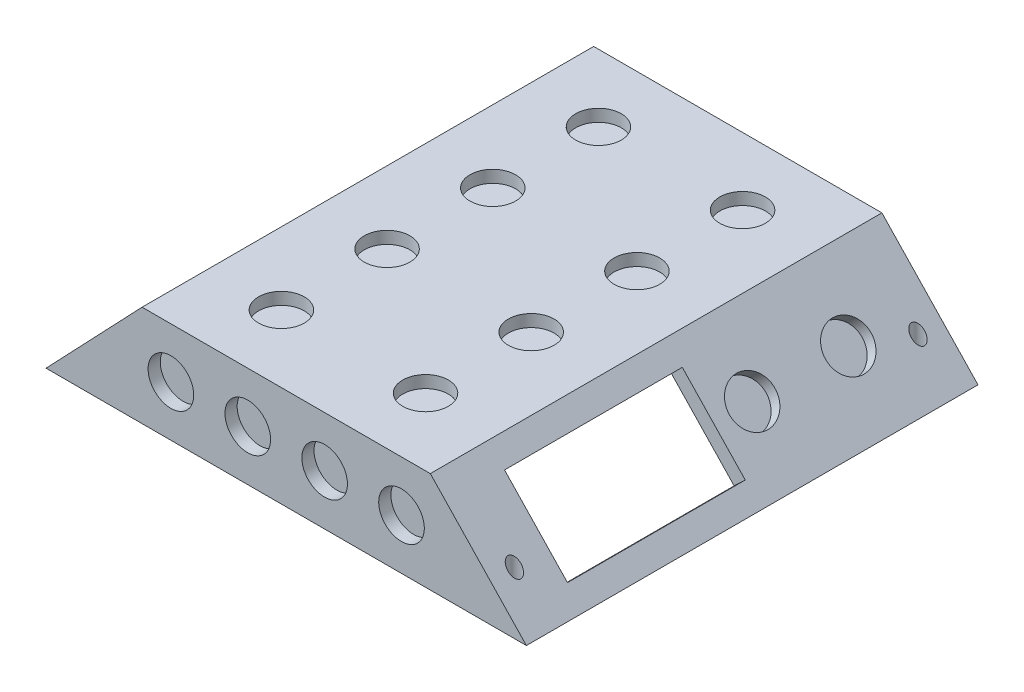
SolidWorks part; units mm, degrees
ref_plane "Alzado" through (0, 0, 0) normal (0, 0, 1) x (1, 0, 0)
ref_plane "Planta" through (0, 0, 0) normal (0, 1, 0) x (1, 0, 0)
ref_plane "Vista lateral" through (0, 0, 0) normal (1, 0, 0) x (0, 0, -1)
sketch "Croquis2" plane through (0, 0, 0) normal (0, 0, 1) x (1, 0, 0)
  line L0 (-50, 0) -> (-30, 0)
  line L1 (-30, 0) -> (-30, 21)
  line L2 (-30, 21) -> (-50, 0)
  line L3 (30, 21) -> (50, 0)
  line L4 (-30, 21) -> (30, 21)
  line L5 (-30, 21) -> (-30, 0)
  line L6 (-30, 0) -> (30, 0)
  line L7 (30, 21) -> (30, 0)
  line L8 (50, 0) -> (30, 0)
  dimension "D1" = 100
  dimension "D2" = 60
  dimension "D3" = 21
extrude "Saliente-Extruir1" add sketch "Croquis2" along normal blind 94 contours L7 L4 L1 L6 | L1 L2 L0 | L8 L3 L7 region at (-36.6667, 7, 0) region at (0, 10.5, 0) region at (36.6667, 7, 0)
sketch "Croquis3" plane through (0, 0, 0) normal (0, 0, -1) x (-1, 0, 0)
  line L0 (-45.581, 0) -> (-28.6286, 17.8)
  line L1 (50, 0) -> (-50, 0) construction
  line L2 (-28.6286, 17.8) -> (28.6286, 17.8)
  line L3 (28.6286, 17.8) -> (45.581, 0)
  line L4 (45.581, 0) -> (-45.581, 0)
  line L5 (-30, 21) -> (-50, 0) construction
  line L6 (30, 21) -> (-30, 21) construction
  line L9 (30, 21) -> (50, 0) construction
  line L11 (50, 0) -> (45.581, 0)
  line M1 (-50, 0) -> (50, 0)
  dimension "D1" = 3.2
  dimension "D2" = 3.2
  dimension "D3" = 3.2
extrude "Cortar-Extruir1" cut sketch "Croquis3" against normal blind 91 contours L3 L2 L0 M1 region at (0, 8.2223, 0)
sketch "Croquis7" plane through (0, 21, 0) normal (0, 1, 0) x (1, 0, 0)
  line L0 (-50, -94) -> (-50, 0) construction
  line L1 (-50, 0) -> (50, 0) construction
  line L2 (50, 0) -> (50, -94) construction
  line L3 (50, -94) -> (-50, -94) construction
  line L4 (-42.5, 0) -> (-42.5, -94) construction
  line L5 (-50, -5) -> (50, -5) construction
  line L6 (42.5, 0) -> (42.5, -94) construction
  line L7 (-50, -89) -> (50, -89) construction
  line L8 (0, 0) -> (0, -94) construction
  dimension "D1" = 5
  dimension "D2" = 42.5
  dimension "D3" = 42.5
  dimension "D4" = 5
hole_wizard "Taladro de margen para M2.51" positions "Croquis11" profile "Croquis10" hole size "M2.5" standard "ISO" end condition through all
sketch "Croquis11" plane through (0, 21, 0) normal (0, 1, 0) x (1, 0, 0)
  line L0 (-42.5, 0) -> (-42.5, -94) construction
  line L1 (-50, -5) -> (50, -5) construction
  line L2 (42.5, 0) -> (42.5, -94) construction
  line L3 (-50, -89) -> (50, -89) construction
  point P0 (-42.5, -5)
  point P6 (42.5, -5)
  point P10 (-42.5, -89)
  point P14 (42.5, -89)
sketch "Croquis10" plane through (-42.5, 21, 5) normal (1, 0, 0) x (0, 0, 1)
  line L0 (0, 0) -> (0, 21)
  line L1 (0, 21) -> (1.35, 21)
  line L2 (1.35, 21) -> (1.35, 0)
  line L5 (1.35, 0) -> (0, 0)
  line L11 (0, -6.35) -> (0, 107.95) construction
  dimension "Diámetro de taladro hasta el siguiente" = 2.7
  dimension "Profundidad de taladro hasta el siguiente" = 21
sketch "Croquis12" plane through (26.2188, 24.9703, 0) normal (0.7241, 0.6897, 0) x (0, 0, -1)
  line L0 (-94, -5.4828) -> (0, -5.4828) construction
  line L1 (-82, -10.4828) -> (-45, -10.4828)
  line L2 (-82, -10.4828) -> (-82, -29.4828)
  line L3 (-82, -29.4828) -> (-45, -29.4828)
  line L4 (-45, -10.4828) -> (-45, -29.4828)
  line L5 (-94, -34.4828) -> (0, -34.4828) construction
  line L6 (-94, -5.4828) -> (-94, -34.4828) construction
  dimension "D1" = 5
  dimension "D2" = 5
  dimension "D3" = 12
  dimension "D4" = 37
extrude "Cortar-Extruir2" cut sketch "Croquis12" against normal up to next
sketch "Croquis13" plane through (0, 21, 0) normal (0, 1, 0) x (1, 0, 0)
  line L0 (0, 0) -> (0, -94) construction
  line L1 (-30, 0) -> (30, 0) construction
  line L2 (-30, -94) -> (30, -94) construction
  circle A0 centre (-15, -14) radius 4.75
  circle A1 centre (-15, -36) radius 4.75
  circle A2 centre (-15, -58) radius 4.75
  circle A3 centre (-15, -80) radius 4.75
  circle A4 centre (15, -14) radius 4.75
  circle A5 centre (15, -36) radius 4.75
  circle A6 centre (15, -58) radius 4.75
  circle A7 centre (15, -80) radius 4.75
  dimension "D1" = 9.5
  dimension "D2" = 14
  dimension "D3" = 22
  dimension "D4" = 14
  dimension "D5" = 22
  dimension "D6" = 22
  dimension "D7" = 15
extrude "Cortar-Extruir3" cut sketch "Croquis13" against normal blind 2.54
sketch "Croquis14" plane through (-26.2188, 24.9703, 0) normal (-0.7241, 0.6897, 0) x (0, 0, 1)
  line L0 (0, -19.9828) -> (94, -19.9828) construction
  line L1 (0, -5.4828) -> (0, -34.4828) construction
  line L2 (94, -5.4828) -> (94, -34.4828) construction
  circle A0 centre (17, -19.9828) radius 4.75
  circle A1 centre (37, -19.9828) radius 4.75
  circle A2 centre (57, -19.9828) radius 4.75
  circle A3 centre (77, -19.9828) radius 4.75
  point P16 (59.4599, -20.9096)
  dimension "D1" = 9.5
  dimension "D2" = 17
  dimension "D3" = 20
  dimension "D4" = 17
  dimension "D5" = 20
  dimension "D6" = 20
extrude "Cortar-Extruir4" cut sketch "Croquis14" against normal blind 2.54
sketch "Croquis15" plane through (26.2188, 24.9703, 0) normal (0.7241, 0.6897, 0) x (0, 0, -1)
  line L0 (0, -19.9828) -> (-94, -19.9828) construction
  line L1 (0, -5.4828) -> (0, -34.4828) construction
  line L2 (-94, -5.4828) -> (-94, -34.4828) construction
  circle A0 centre (-17, -19.9828) radius 4.75
  circle A1 centre (-37, -19.9828) radius 4.75
  dimension "D1" = 9.5
  dimension "D2" = 17
  dimension "D3" = 20
extrude "Cortar-Extruir5" cut sketch "Croquis15" against normal blind 2.54
sketch "Croquis17" plane through (0, 0, 94) normal (0, 0, 1) x (1, 0, 0)
  line L0 (0, 21) -> (0, 0) construction
  line L1 (-30, 21) -> (30, 21) construction
  line L2 (-50, 0) -> (50, 0) construction
  line L3 (-40, 10.5) -> (40, 10.5) construction
  line L4 (-30, 21) -> (-50, 0) construction
  line L5 (30, 21) -> (50, 0) construction
  circle A0 centre (-8, 10.5) radius 4.75
  circle A1 centre (8, 10.5) radius 4.75
  circle A2 centre (-24, 10.5) radius 4.75
  circle A3 centre (24, 10.5) radius 4.75
  dimension "D1" = 9.5
  dimension "D2" = 8
  dimension "D3" = 16
extrude "Cortar-Extruir7" cut sketch "Croquis17" against normal blind 2.54
